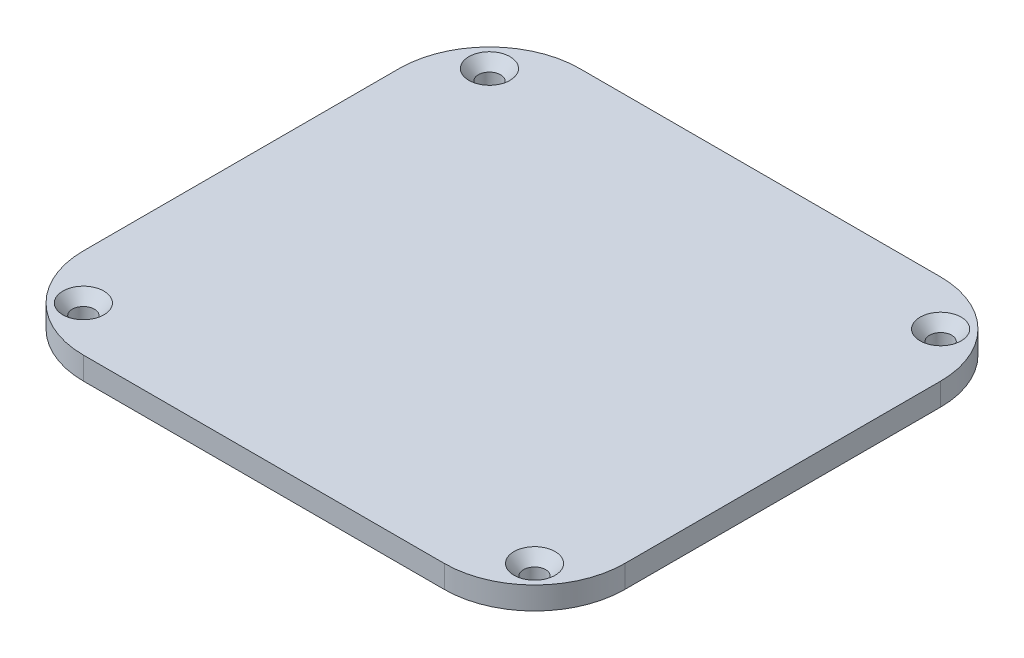
SolidWorks part; units mm, degrees
material "ABS"
ref_plane "Front Plane" through (0, 0, 0) normal (0, 0, 1) x (1, 0, 0)
ref_plane "Top Plane" through (0, 0, 0) normal (0, 1, 0) x (1, 0, 0)
ref_plane "Right Plane" through (0, 0, 0) normal (1, 0, 0) x (0, 0, -1)
sketch "Sketch1" plane through (0, 0, 0) normal (0, 1, 0) x (1, 0, 0)
  line L0 (-60, -30) -> (-60, 40)
  line L1 (-40, 60) -> (40, 60)
  line L2 (60, 40) -> (60, -30)
  line L3 (40, -50) -> (-40, -50)
  line L4 (-40, -22) -> (42.5, -22) construction
  line L5 (-40, -22) -> (-40, -32) construction
  line L6 (-30, -42) -> (32.5, -42) construction
  line L7 (42.5, -22) -> (42.5, -32) construction
  line L8 (2.5, 55) -> (2.5, 30) construction
  line L9 (2.5, 30) -> (42.5, 30) construction
  line L10 (30.5, 55) -> (2.5, 55) construction
  line L11 (42.5, 43) -> (42.5, 30) construction
  line L12 (-39.4, -22.6) -> (41.9, -22.6)
  line L13 (41.9, -22.6) -> (41.9, -32)
  line L14 (-30, -41.4) -> (32.5, -41.4)
  line L15 (-39.4, -22.6) -> (-39.4, -32)
  line L16 (3.1, 54.4) -> (3.1, 30.6)
  line L17 (3.1, 30.6) -> (41.9, 30.6)
  line L18 (41.9, 43) -> (41.9, 30.6)
  line L19 (30.5, 54.4) -> (3.1, 54.4)
  arc A0 (60, -30) -> (40, -50) centre (40, -30) cw
  arc A1 (60, 40) -> (40, 60) centre (40, 40) ccw
  arc A2 (-60, 40) -> (-40, 60) centre (-40, 40) cw
  arc A3 (-40, -50) -> (-60, -30) centre (-40, -30) cw
  arc A4 (-30, -42) -> (-40, -32) centre (-30, -32) cw construction
  arc A5 (42.5, -32) -> (32.5, -42) centre (32.5, -32) cw construction
  arc A6 (42.5, 43) -> (30.5, 55) centre (30.5, 43) ccw construction
  arc A7 (41.9, -32) -> (32.5, -41.4) centre (32.5, -32) cw
  arc A8 (-30, -41.4) -> (-39.4, -32) centre (-30, -32) cw
  arc A9 (41.9, 43) -> (30.5, 54.4) centre (30.5, 43) ccw
  dimension "D4" = 12
  dimension "D7" = 20
  dimension "D11" = 40
  dimension "D14" = 10
  dimension "D15" = 0.6
  dimension "D12" = 20
  dimension "D1" = 70
  dimension "D2" = 80
  dimension "D3" = 60
  dimension "D5" = 60
  dimension "D6" = 8
  dimension "D8" = 25
  dimension "D9" = 30
  dimension "D10" = 57.5
  dimension "D13" = 20
  dimension "D16" = 0.6
extrude "Boss-Extrude1" add sketch "Sketch1" along normal blind 5 contours L11 A6 L10 L8 L9 | A5 L7 L4 L5 A4 L6 | A3 L0 A2 L1 A1 L2 A0 L3
extrude "Boss-Extrude2" add sketch "Sketch1<5>" against normal blind 4.4 contours A5 L7 L4 L5 A4 L6 | L11 A6 L10 L8 L9 | L18 A9 L19 L16 L17 | A8 L14 A7 L13 L12 L15 region at (1.25, 0, 31.8143) region at (21.9751, 0, -42.2087)
sketch "Sketch1<5>" plane through (0, 0, 0) normal (0, 1, 0) x (1, 0, 0) same geometry as "Sketch1"
sketch "Sketch4" plane through (0, 5, 0) normal (0, 1, 0) x (1, 0, 0)
  line L0 (-60, -30) -> (-60, 40) construction
  line L1 (40, -50) -> (-40, -50) construction
  line L2 (60, 40) -> (60, -30) construction
  line L3 (40, -50) -> (-40, -50) construction
  line L4 (60, 40) -> (60, -30) construction
  line L5 (-40, 60) -> (40, 60) construction
  line L6 (-60, -30) -> (-60, 40) construction
  circle A0 centre (-20.2, -7) radius 4.9
  circle A1 centre (-43.84, -2.83) radius 4.9
  circle A2 centre (3.44, 12.83) radius 4.9
  circle A3 centre (44.41, -4.14) radius 4.9
  circle A4 centre (27.44, 12.83) radius 4.9
  point P16 (50, -40)
  point P17 (50, 50)
  point P18 (-50, -40)
  point P19 (-50, 50)
  dimension "D1" = 9.8
  dimension "D2" = 16.16
  dimension "D3" = 47.17
  dimension "D4" = 39.8
  dimension "D5" = 43
  dimension "D6" = 62.83
  dimension "D7" = 63.44
  dimension "D8" = 62.83
  dimension "D9" = 87.44
  dimension "D10" = 45.86
  dimension "D11" = 15.59
  dimension "D12" = 10
  dimension "D13" = 10
  dimension "D14" = 10
  dimension "D15" = 10
  dimension "D16" = 10
  dimension "D17" = 10
  dimension "D18" = 10
  dimension "D19" = 10
extrude "Cut-Extrude2" cut sketch "Sketch4" along normal blind 1.5 from surface starting at face at (0, 0, -5)
hole_wizard "CSK for #8 Flat Head Socket Cap Screw1" positions "3DSketch1" profile "Sketch5" countersink size "#8" standard "ANSI Inch"
sketch3d "3DSketch1"
  point P0 (50, 5, 40)
  point P3 (50, 5, -50)
  point P6 (-50, 5, -50)
  point P9 (-50, 5, 40)
sketch "Sketch5" plane through (50, 5, 40) normal (1, 0, 0) x (0, 0, 1)
  line L0 (0, 0) -> (0, 69.8166)
  line L1 (0, 69.8166) -> (2.4574, 68.34)
  line L2 (2.4574, 68.34) -> (2.4574, 2.4179)
  line L3 (2.4574, 2.4179) -> (4.5593, 0)
  line L5 (4.5593, 0) -> (0, 0)
  line L6 (-2.4574, 2.4179) -> (-4.5593, 0) construction
  line L10 (0, 69.8166) -> (-2.4575, 68.34) construction
  line L11 (0, -6.35) -> (0, 107.95) construction
  dimension "Hole Dia." = 4.9149
  dimension "Hole Depth" = 68.34
  dimension "Near C'Sink Dia." = 9.1186
  dimension "Near C'Sink Angle" = 82
  dimension "Drill Angle" = 118
